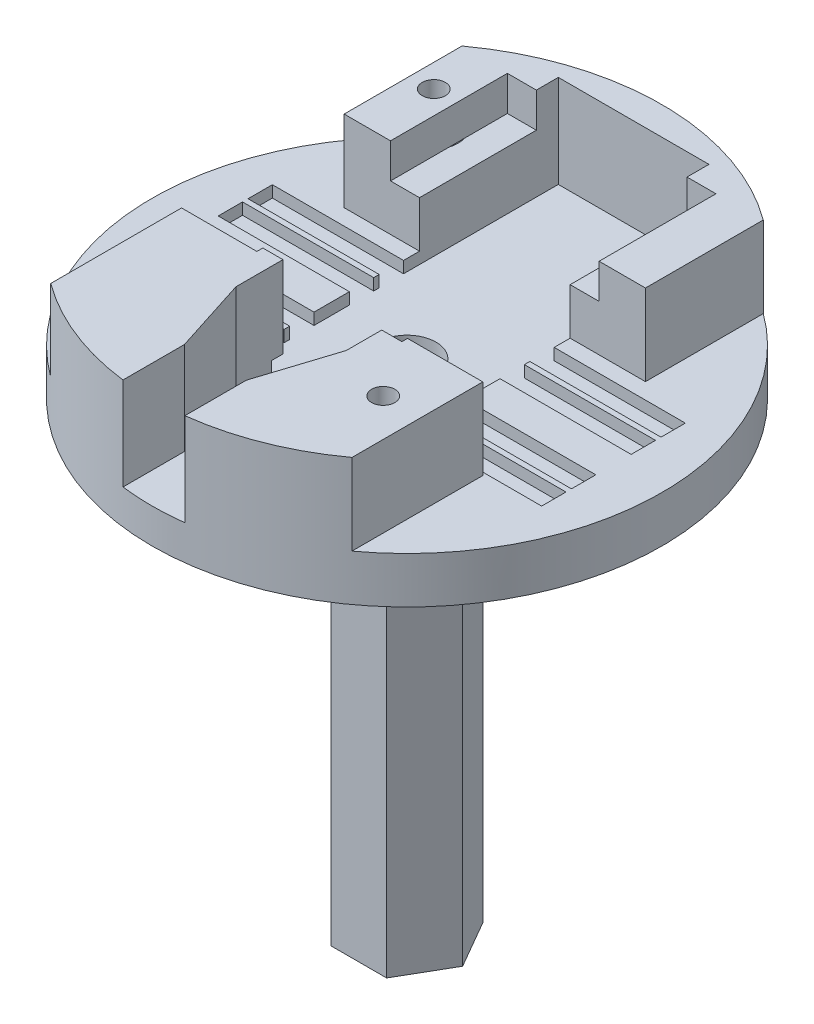
SolidWorks part; units mm, degrees
ref_plane "Front Plane" through (0, 0, 0) normal (0, 0, 1) x (1, 0, 0)
ref_plane "Top Plane" through (0, 0, 0) normal (0, 1, 0) x (1, 0, 0)
ref_plane "Right Plane" through (0, 0, 0) normal (1, 0, 0) x (0, 0, -1)
sketch "Sketch1" plane through (0, 0, 0) normal (0, 1, 0) x (1, 0, 0)
  circle A0 centre (0, 0) radius 22
extrude "Boss-Extrude1" add sketch "Sketch1" along normal blind 9 and the other way blind 2
sketch "Sketch2" plane through (0, 9, 0) normal (0, 1, 0) x (1, 0, 0)
  line L0 (0, 0) -> (0, -22) construction
  circle A0 centre (0, 0) radius 22 construction
ref_plane "Plane4" through (0, -2, 0) normal (0, -1, 0) x (-1, 0, 0)
sketch "Sketch6" plane through (0, -2, 0) normal (0, -1, 0) x (-1, 0, 0)
  circle A0 centre (0, 0) radius 21
  circle A1 centre (0, 0) radius 12.5
extrude "Cut-Extrude5" cut sketch "Sketch6" against normal blind 1
sketch "Sketch7" plane through (0, -2, 0) normal (0, -1, 0) x (-1, 0, 0)
  circle A0 centre (0, 0) radius 8.5
extrude "Boss-Extrude2" add sketch "Sketch7" along normal blind 40 contours A0
sketch "Sketch8" plane through (0, -2, 0) normal (0, -1, 0) x (-1, 0, 0)
  circle A0 centre (0, 0) radius 1.5
extrude "Cut-Extrude6" cut sketch "Sketch8" against normal through all and the other way through all contours A0
sketch "Sketch9" plane through (0, 9, 0) normal (0, 1, 0) x (1, 0, 0)
  line L0 (0, 0) -> (-13.0007, 0) construction
  line L1 (-13.0007, -20.3592) -> (-13.0007, 20.3592)
  line L2 (13, -20.3597) -> (13, 20.3597)
  line L3 (0, 0) -> (13, 0) construction
  arc A0 (13, -20.3597) -> (13, 20.3597) centre (0, 0) ccw
  arc A1 (-13.0007, 20.3592) -> (-13.0007, -20.3592) centre (0, 0) ccw
extrude "Cut-Extrude7" cut sketch "Sketch9" against normal blind 7
ref_plane "Plane5" through (0, -42, 0) normal (0, -1, 0) x (-1, 0, 0)
sketch "Sketch17" plane through (0, -42, 0) normal (0, -1, 0) x (-1, 0, 0)
  circle A0 centre (0, 0) radius 2.4968
extrude "Cut-Extrude14" cut sketch "Sketch17" against normal blind 62
ref_plane "Plane6" through (0, 9, 0) normal (0, 1, 0) x (1, 0, 0)
sketch "Sketch18" plane through (0, 9, 0) normal (0, 1, 0) x (1, 0, 0)
  line L0 (0, -22.0336) -> (0, 23.1421) construction
sketch "Sketch23" plane through (0, 9, 0) normal (0, 1, 0) x (1, 0, 0)
  line L0 (-2.6704, -16.8582) -> (-2.6704, -16.5304)
  line L1 (6.5, 19.5569) -> (6.5, -6.9431)
  line L2 (-6.5, 19.5569) -> (-6.5, -6.9431)
  line L3 (0, -25.25) -> (0, 0) construction
  line L4 (2.6704, -16.8582) -> (2.6704, -16.5304)
  line L5 (4.7624, -10) -> (2.5704, -16.8425) construction
  line L6 (-4.7624, -10) -> (-2.5704, -16.8425) construction
  line L7 (-4.7624, -10) -> (-2.6704, -16.5304)
  line L8 (0, -25.25) -> (-1.0006, -21.9772)
  line L9 (-6.5, 19.5569) -> (6.5, 19.5569)
  line L10 (-6.5, -6.9431) -> (-4.7624, -6.9431)
  line L11 (6.5, -6.9431) -> (4.7624, -6.9431)
  line L12 (-2.6704, -16.8582) -> (-2.6704, -21.9381) construction
  line L13 (2.6704, -16.8582) -> (2.6704, -21.9381) construction
  line L15 (1.0006, -21.9772) -> (0, -25.25)
  line L16 (4.7624, -10) -> (2.6704, -16.5304)
  line L17 (-2.6704, -16.8582) -> (-2.6704, -21.8373)
  line L19 (-4.7624, -10) -> (-4.7624, -6.9431)
  line L21 (4.7624, -10) -> (4.7624, -6.9431)
  line L22 (2.6704, -16.8582) -> (2.6704, -21.8373)
  line L32 (0, -25.592) -> (-1.0756, -22.0738) construction
  line L33 (1.0756, -22.0738) -> (0, -25.592) construction
  line L34 (4.8624, -10.0156) -> (2.6704, -16.8582) construction
  line L35 (4.8624, -10.0156) -> (4.8624, -7.0431) construction
  line L36 (6.6, -7.0431) -> (4.8624, -7.0431) construction
  line L37 (6.6, 19.6569) -> (6.6, -7.0431) construction
  line L38 (-6.6, 19.6569) -> (6.6, 19.6569) construction
  line L39 (-6.6, 19.6569) -> (-6.6, -7.0431) construction
  line L40 (-6.6, -7.0431) -> (-4.8624, -7.0431) construction
  line L41 (-4.8624, -10.0156) -> (-4.8624, -7.0431) construction
  line L42 (-4.8624, -10.0156) -> (-2.6704, -16.8582) construction
  line L43 (2.5704, -16.8425) -> (2.5704, -21.8493) construction
  line L44 (-2.5704, -16.8425) -> (-2.5704, -21.8493) construction
  arc A0 (-2.6704, -21.8373) -> (-1.0006, -21.9772) centre (0, 0) ccw
  arc A1 (1.0006, -21.9772) -> (2.6704, -21.8373) centre (0, 0) ccw
  arc A4 (1.0756, -22.0738) -> (2.6704, -21.9381) centre (0, 0) ccw construction
  arc A5 (-2.6704, -21.9381) -> (-1.0756, -22.0738) centre (0, 0) ccw construction
  arc A6 (-2.5704, -21.8493) -> (-1.0006, -21.9772) centre (0, 0) ccw construction
  arc A7 (1.0006, -21.9772) -> (2.5704, -21.8493) centre (0, 0) ccw construction
  dimension "D1" = 180
ref_plane "Plane10" through (0, 0, 6.4558) normal (0, 0, -1) x (-1, 0, 0)
sketch "Sketch29" plane through (0, 9, 0) normal (0, 1, 0) x (1, 0, 0)
  line L0 (9, 17.6622) -> (9, -6.4558)
  line L1 (9, 17.6622) -> (-9, 17.6622)
  line L2 (9, -6.4558) -> (-9, -6.4558)
  line L3 (0, -6.4558) -> (0, 17.6622) construction
  line L4 (-9, -6.4558) -> (-9, 17.6622)
  point P5 (0, -6.4558)
  point P8 (0, 17.6622)
extrude "Cut-Extrude19" cut sketch "Sketch29" against normal blind 3
sketch "Sketch30" plane through (0, 9, 0) normal (0, 1, 0) x (1, 0, 0)
  line L0 (-8.0021, 17.6622) -> (-8.0021, -6.4558) construction
  line L1 (8.0021, -6.4558) -> (5.5021, -6.4558)
  line L2 (8.0021, -6.4558) -> (8.0021, 7.5442)
  line L3 (8.0021, 7.5442) -> (5.5021, 7.5442)
  line L4 (-8.0021, -6.4558) -> (-8.0021, 7.5442)
  line L5 (5.5021, 7.5442) -> (5.5021, -6.4558)
  line L8 (-5.5021, 7.5442) -> (-5.5021, -6.4558)
  line L9 (-5.5021, 7.5442) -> (-8.0021, 7.5442)
  line L10 (-5.5021, -6.4558) -> (-8.0021, -6.4558)
  point P7 (5.5021, 7.5442)
  dimension "D1" = 2.5
extrude "Cut-Extrude20" cut sketch "Sketch30" against normal blind 6
ref_plane "Plane11" through (0, 3, 0) normal (0, -1, 0) x (-1, 0, 0)
sketch "Sketch32" plane through (0, 3, 0) normal (0, -1, 0) x (-1, 0, 0)
  circle A1 centre (-5.1962, -3) radius 0.85
  circle A3 centre (5.1962, -3) radius 0.85
  circle A5 centre (5.1962, 3) radius 0.85
  circle A6 centre (-5.1962, 3) radius 0.85
  circle A7 centre (0, 6) radius 0.0479
  circle A8 centre (0, 6) radius 0.85
  circle A9 centre (0, -6) radius 0.85
extrude "Cut-Extrude22" [suppressed] cut sketch "Sketch32" against normal blind 11 and the other way through all
ref_plane "Plane12" through (0, 2, 0) normal (0, 1, 0) x (1, 0, 0)
sketch "Sketch33" [suppressed] plane through (0, 2, 0) normal (0, 1, 0) x (1, 0, 0)
  circle A0 centre (5.1962, 3) radius 1.1
  circle A1 centre (5.1962, -3) radius 1.1
  circle A2 centre (-5.1962, 3) radius 1.1
  circle A3 centre (-5.1962, -3) radius 1.1
  circle A4 centre (0, -6) radius 1.1
  circle A5 centre (0, 6) radius 1.1
extrude "Cut-Extrude23" [suppressed] cut sketch "Sketch33" against normal blind 2 and the other way through all
ref_plane "Plane13" through (0, 2, 0) normal (0, 1, 0) x (1, 0, 0)
sketch "Sketch34" plane through (0, 2, 0) normal (0, 1, 0) x (1, 0, 0)
  line L0 (-1.3341, 5.3583) -> (7.9939, 5.3583)
  line L1 (-7.985, 6.6083) -> (-1.2507, 6.6083)
  line L2 (-7.985, 6.6083) -> (-7.985, 5.3583)
  line L3 (-7.985, 5.3583) -> (-1.3341, 5.3583)
  line L4 (7.9939, 6.6083) -> (7.9939, 5.3583)
  line L5 (-1.2507, 6.6083) -> (7.9939, 6.6083)
  line L6 (8.0021, -6.4558) -> (-8.0021, -6.4558)
  line L7 (-8.0021, -6.4558) -> (-8.0021, -5.2058)
  line L8 (-8.0021, 7.5442) -> (-8.0021, -6.4558) construction
  line L9 (-8.0021, -5.2058) -> (8.0021, -5.2058)
  line L10 (8.0021, -5.2058) -> (8.0021, -6.4558)
extrude "Cut-Extrude27" [suppressed] cut sketch "Sketch34" against normal blind 2
ref_plane "Plane14" through (0, -6.5, 0) normal (0, 1, 0) x (1, 0, 0)
sketch "Sketch35" plane through (0, -6.5, 0) normal (0, 1, 0) x (1, 0, 0)
  circle A0 centre (0, 0) radius 8.5
  circle A1 centre (0, 0) radius 9.1
extrude "Boss-Extrude4" add sketch "Sketch35" along normal blind 2 and the other way blind 2
ref_plane "Plane15" through (0, -17, 0) normal (0, 1, 0) x (1, 0, 0)
sketch "Sketch36" plane through (0, -17, 0) normal (0, 1, 0) x (1, 0, 0)
  circle A0 centre (0, 0) radius 8.3
  circle A1 centre (0, 0) radius 8.5
extrude "Cut-Extrude28" cut sketch "Sketch36" against normal blind 1.5 and the other way blind 1.5
ref_plane "Plane16" through (0, -21, 0) normal (0, 1, 0) x (1, 0, 0)
ref_plane "Plane17" through (0, -25, 0) normal (0, 1, 0) x (1, 0, 0)
ref_plane "Plane18" through (0, -29, 0) normal (0, 1, 0) x (1, 0, 0)
ref_plane "Plane19" through (0, -33, 0) normal (0, 1, 0) x (1, 0, 0)
ref_plane "Plane20" through (0, -37, 0) normal (0, 1, 0) x (1, 0, 0)
sketch "Sketch39" plane through (0, -21, 0) normal (0, 1, 0) x (1, 0, 0)
  circle A0 centre (0, 0) radius 8.3
  circle A1 centre (0, 0) radius 8.5
extrude "Cut-Extrude30" cut sketch "Sketch39" against normal blind 1.5 and the other way blind 1.5
sketch "Sketch40" plane through (0, -25, 0) normal (0, 1, 0) x (1, 0, 0)
  circle A0 centre (0, 0) radius 8.3
  circle A1 centre (0, 0) radius 8.5
extrude "Cut-Extrude31" cut sketch "Sketch40" against normal blind 1.5 and the other way blind 1.5
sketch "Sketch41" plane through (0, -29, 0) normal (0, 1, 0) x (1, 0, 0)
  circle A0 centre (0, 0) radius 8.35
  circle A1 centre (0, 0) radius 8.5
extrude "Cut-Extrude32" cut sketch "Sketch41" against normal blind 1.5 and the other way blind 1.5
sketch "Sketch42" plane through (0, -33, 0) normal (0, 1, 0) x (1, 0, 0)
  circle A0 centre (0, 0) radius 8.3
  circle A1 centre (0, 0) radius 8.5
extrude "Cut-Extrude33" cut sketch "Sketch42" against normal blind 1.5 and the other way blind 1.5
sketch "Sketch43" plane through (0, -37, 0) normal (0, 1, 0) x (1, 0, 0)
  circle A0 centre (0, 0) radius 8.3
  circle A1 centre (0, 0) radius 8.5
extrude "Cut-Extrude34" cut sketch "Sketch43" against normal blind 1.5 and the other way blind 1.5
sketch "Sketch44" plane through (0, 0, 0) normal (0, 0, 1) x (1, 0, 0)
  line L0 (0, 0) -> (0, -16.9756) construction
  line L1 (0, -16.9756) -> (0, -29.0422) construction
  circle A0 centre (0, -16.9756) radius 1
  circle A1 centre (0, -29.0422) radius 1
extrude "Cut-Extrude35" cut sketch "Sketch44" against normal through all and the other way through all
ref_axis "Axis1" through (0, -42, 0) along (0, 1, 0)
ref_plane "Plane21" through (0, 0, 0) normal (0.866, 0, 0.5) x (0, 1, 0)
sketch "Sketch45" plane through (0, 0, 0) normal (0.866, 0, 0.5) x (0, 1, 0)
  line L0 (0, 0) -> (-21.1015, 0) construction
  line L1 (-21.1015, 0) -> (-33.0495, 0) construction
  circle A0 centre (-21.1015, 0) radius 1
  circle A1 centre (-33.0495, 0) radius 1
extrude "Cut-Extrude36" cut sketch "Sketch45" against normal through all and the other way through all
ref_plane "Plane22" through (0, 0, 0) normal (0.866, 0, -0.5) x (0, 1, 0)
sketch "Sketch46" plane through (0, 0, 0) normal (0.866, 0, -0.5) x (0, 1, 0)
  line L0 (0, 0) -> (-24.961, 0) construction
  line L1 (-24.961, 0) -> (-37.1304, 0) construction
  circle A0 centre (-24.961, 0) radius 1
  circle A1 centre (-37.1304, 0) radius 1
extrude "Cut-Extrude37" cut sketch "Sketch46" against normal through all and the other way through all
ref_plane "Plane23" through (0, 9, 0) normal (0, 1, 0) x (1, 0, 0)
sketch "Sketch47" plane through (0, 9, 0) normal (0, 1, 0) x (1, 0, 0)
  line L1 (13.8544, -6.4558) -> (-13.8777, -6.4558)
  line L2 (13.8544, -6.4558) -> (13.8544, 7.5778)
  line L3 (13.8544, 7.5778) -> (-13.8777, 7.5778)
  line L4 (-13.8777, -6.4558) -> (-13.8777, 7.5778)
extrude "Cut-Extrude38" cut sketch "Sketch47" against normal blind 7
extrude "Cut-Extrude39" cut sketch "Sketch23" against normal blind 8
sketch "Sketch48" plane through (0, 9, 0) normal (0, 1, 0) x (1, 0, 0)
  line L0 (0, 0) -> (0, 34.87) construction
  line L1 (11, 7.5778) -> (11, 19.0526) construction
  line L2 (13, 7.5778) -> (9, 7.5778) construction
  line L3 (11, 19.0526) -> (11, 13.3152) construction
  line L4 (11, 13.3152) -> (0, 0) construction
  line L5 (0, 0) -> (-17.1456, -20.7543) construction
  line L6 (-9.7504, -6.4558) -> (-9.7504, -16.5924) construction
  line L7 (-13.0007, -6.4558) -> (-6.5, -6.4558) construction
  arc A0 (13, 17.7482) -> (-13.0007, 17.7477) centre (0, 0) ccw construction
  circle A3 centre (-11, 13.3152) radius 1
  circle A4 centre (9.7504, -11.8025) radius 1
  dimension "D1" = 39.561
extrude "Cut-Extrude40" cut sketch "Sketch48" against normal blind 9
sketch "Sketch49" plane through (0, -1, 0) normal (0, -1, 0) x (1, 0, 0)
  circle A2 centre (-11, -13.3152) radius 2.1
  circle A3 centre (9.7504, 11.8025) radius 2.1
sketch "Sketch50" plane through (0, -42, 0) normal (0, -1, 0) x (1, 0, 0)
  line L0 (4.9897, 0.0006) -> (-4.9897, -0.0006) construction
  line L2 (-4.9897, -0.0006) -> (-2.4943, -4.3215)
  line L3 (-2.4943, -4.3215) -> (2.4953, -4.3209)
  line L4 (2.4953, -4.3209) -> (4.9897, 0.0006)
  line L5 (4.9897, 0.0006) -> (2.4943, 4.3215)
  line L6 (2.4943, 4.3215) -> (-2.4953, 4.3209)
  line L7 (-2.4953, 4.3209) -> (-4.9897, -0.0006)
  circle A0 centre (0, 0) radius 4.3212 construction
  circle A1 centre (0, 0) radius 6.3883
extrude "Boss-Extrude5" add sketch "Sketch50" against normal blind 2
sketch "Sketch51" plane through (0, 2, 0) normal (0, 1, 0) x (1, 0, 0)
  line L1 (-4.46, 2.575) -> (4.46, 2.575) construction
  line L3 (-17.8187, 4.1) -> (17.8187, 4.1)
  line L4 (-17.8187, 4.1) -> (-17.8187, 6.2)
  line L5 (-17.8187, 6.2) -> (17.8187, 6.2)
  line L6 (17.8187, 4.1) -> (17.8187, 6.2)
  line L7 (-17.8187, 4.1) -> (17.8187, 6.2) construction
  line L8 (-17.8187, 6.2) -> (17.8187, 4.1) construction
  line L9 (-4.46, -2.575) -> (4.46, -2.575) construction
  line L10 (-17.8187, 3.625) -> (17.8187, 3.625)
  line L11 (-17.8187, 3.625) -> (-17.8187, 1.525)
  line L12 (-17.8187, 1.525) -> (17.8187, 1.525)
  line L13 (17.8187, 3.625) -> (17.8187, 1.525)
  line L14 (-17.8187, 3.625) -> (17.8187, 1.525) construction
  line L15 (-17.8187, 1.525) -> (17.8187, 3.625) construction
  line L17 (-17.8187, -3.625) -> (17.8187, -3.625)
  line L18 (-17.8187, -3.625) -> (-17.8187, -1.525)
  line L19 (-17.8187, -1.525) -> (17.8187, -1.525)
  line L20 (17.8187, -3.625) -> (17.8187, -1.525)
  line L21 (-17.8187, -3.625) -> (17.8187, -1.525) construction
  line L22 (-17.8187, -1.525) -> (17.8187, -3.625) construction
  line L23 (-17.8187, -6.2) -> (17.8187, -6.2)
  line L24 (-17.8187, -6.2) -> (-17.8187, -4.1)
  line L25 (-17.8187, -4.1) -> (17.8187, -4.1)
  line L26 (17.8187, -6.2) -> (17.8187, -4.1)
  line L27 (-17.8187, -6.2) -> (17.8187, -4.1) construction
  line L28 (-17.8187, -4.1) -> (17.8187, -6.2) construction
  point P0 (0, 5.15)
  point P7 (0, 2.575)
  point P14 (0, -2.575)
  point P22 (0, -5.15)
extrude "Cut-Extrude42" cut sketch "Sketch49" against normal blind 7
extrude "Cut-Extrude43" cut sketch "Sketch51" against normal blind 1
sketch "Sketch53" plane through (0, -42, 0) normal (0, -1, 0) x (1, 0, 0)
  circle A0 centre (0, 0) radius 9.1
extrude "Cut-Extrude45" cut sketch "Sketch53" against normal blind 40
sketch "Sketch55" plane through (0, 0, 6.9431) normal (0, 0, -1) x (-1, 0, 0)
  line L0 (-4.7624, 8) -> (-6.1673, 8)
  line L1 (-6.1673, 8) -> (-6.1673, 6)
  line L2 (-6.1673, 6) -> (-6.5, 6)
  line L3 (-6.5, 6) -> (-6.5, 1.9457)
  line L4 (-6.5, 1.9457) -> (-4.7624, 1.9457)
  line L5 (-4.7624, 1.9457) -> (-4.7624, 8)
  line L6 (6.5, 9) -> (4.7624, 9)
  line L7 (4.7624, 9) -> (4.7624, 1.9457)
  line L8 (4.7624, 1) -> (4.7624, 9) construction
  line L9 (4.7624, 1.9457) -> (6.5, 1.9457)
  line L10 (6.5, 1) -> (6.5, 9) construction
  line L11 (6.5, 1.9457) -> (6.5, 9)
extrude "Boss-Extrude6" add sketch "Sketch55" along normal blind 1
sketch "Sketch56" plane through (0, -2, 0) normal (0, -1, 0) x (1, 0, 0)
  line L1 (2.3995, 4.1572) -> (-2.4005, 4.1566)
  line L2 (-2.4005, 4.1566) -> (-4.8, -0.0006)
  line L3 (-4.8, -0.0006) -> (-2.3995, -4.1572)
  line L4 (-2.3995, -4.1572) -> (2.4005, -4.1566)
  line L5 (2.4005, -4.1566) -> (4.8, 0.0006)
  line L6 (4.8, 0.0006) -> (2.3995, 4.1572)
  circle A0 centre (0, 0) radius 4.1569 construction
extrude "Boss-Extrude9" add sketch "Sketch56" along normal blind 40 and the other way blind 2 separate body
